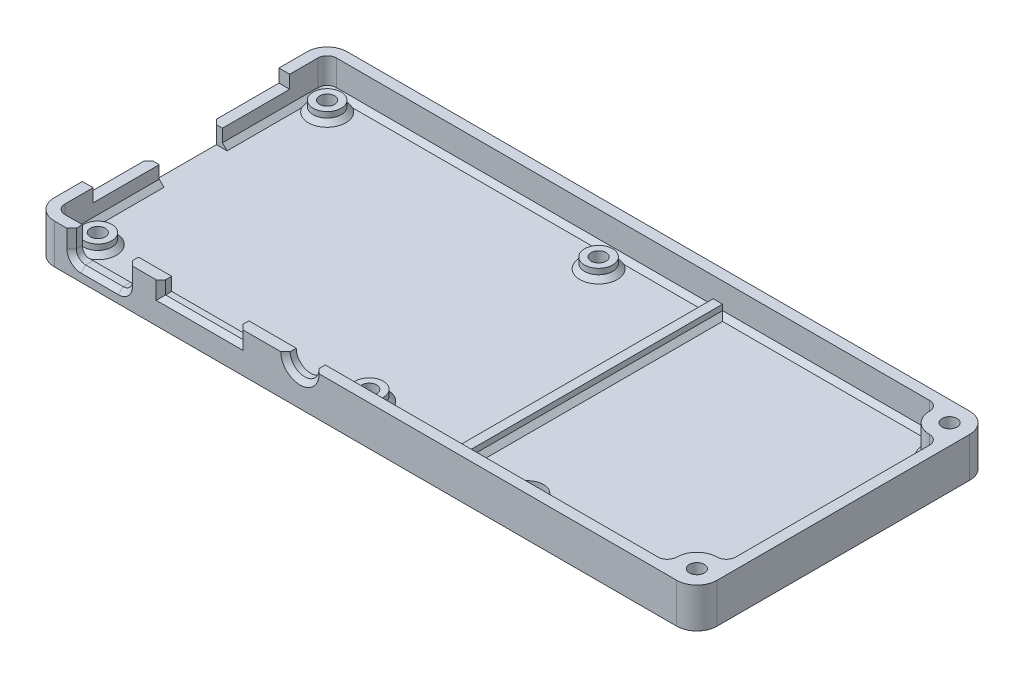
SolidWorks part; units mm, degrees
ref_plane "Front Plane" through (0, 0, 0) normal (0, 0, 1) x (1, 0, 0)
ref_plane "Top Plane" through (0, 0, 0) normal (0, 1, 0) x (1, 0, 0)
ref_plane "Right Plane" through (0, 0, 0) normal (1, 0, 0) x (0, 0, -1)
sketch "Sketch1" plane through (0, 0, 0) normal (0, 1, 0) x (1, 0, 0)
  line L0 (-71.5618, 3.106) -> (63.4382, 3.106) construction
  line L1 (-71.5618, 31.106) -> (63.4382, 31.106)
  line L2 (-71.5618, 31.106) -> (-71.5618, -24.894)
  line L3 (-71.5618, -24.894) -> (63.4382, -24.894)
  line L4 (63.4382, 31.106) -> (63.4382, -24.894)
  line L5 (-60.6618, -24.894) -> (-60.6618, -31.6828) construction
  line L6 (-68.0618, 27.606) -> (-10.0618, 27.606)
  line L7 (-68.0618, 27.606) -> (-68.0618, -21.394)
  line L8 (-68.0618, -21.394) -> (-10.0618, -21.394)
  line L9 (-10.0618, 27.606) -> (-10.0618, -21.394)
  line L10 (-39.5618, -24.894) -> (-39.5618, -31.6828) construction
  line L11 (-18.0618, -24.894) -> (-18.0618, -31.6828) construction
  line L12 (-65.4118, -26.5648) -> (-55.9118, -26.5648) construction
  line L13 (-48.0618, -26.5648) -> (-31.0618, -26.5648) construction
  line L14 (-22.0618, -26.5648) -> (-14.0618, -26.5648) construction
  line L15 (-72.5618, 9.606) -> (-72.5618, -3.394) construction
  line L16 (-71.5618, 3.106) -> (-72.5618, 3.106) construction
  dimension "D1" = 135
  dimension "D2" = 56
  dimension "D3" = 49
  dimension "D4" = 58
  dimension "D5" = 3.5
  dimension "D6" = 3.5
  dimension "D7" = 10.9
  dimension "D8" = 32
  dimension "D9" = 53.5
  dimension "D10" = 2
  dimension "D11" = 13
  dimension "D12" = 9.5
  dimension "D13" = 17
  dimension "D14" = 8
sketch "Sketch3" plane through (0, 0, 0) normal (0, 1, 0) x (1, 0, 0)
  line L4 (66.7382, 34.406) -> (-74.8618, 34.406)
  line L5 (-74.8618, 34.406) -> (-74.8618, -28.194)
  line L6 (-74.8618, -28.194) -> (66.7382, -28.194)
  line L7 (66.7382, -28.194) -> (66.7382, 34.406)
  line L8 (64.4382, 32.106) -> (-72.5618, 32.106)
  line L9 (64.4382, -25.894) -> (64.4382, 32.106)
  line L10 (-72.5618, -25.894) -> (64.4382, -25.894)
  line L11 (-72.5618, 32.106) -> (-72.5618, -25.894)
  line L12 (64.4382, 32.106) -> (-72.5618, 32.106)
  line L13 (64.4382, -25.894) -> (64.4382, 32.106)
  line L14 (-72.5618, -25.894) -> (64.4382, -25.894)
  line L15 (-72.5618, 32.106) -> (-72.5618, -25.894)
  line L16 (-4.0618, 3.106) -> (-4.0618, 34.406) construction
  line L17 (-71.5618, 3.106) -> (63.4382, 3.106) construction
  line L20 (-74.8618, 3.106) -> (52.7382, 3.106) construction
  line L25 (66.7382, -28.194) -> (66.7382, 34.406) construction
  line L26 (64.4382, -25.894) -> (64.4382, 32.106) construction
  dimension "D1" = 1
  dimension "D2" = 2.3
extrude "Boss-Extrude1" add sketch "Sketch3" along normal blind 8.5
sketch "Sketch5" plane through (0, 0, 0) normal (0, 1, 0) x (1, 0, 0)
  line L1 (-72.5618, 32.106) -> (64.4382, 32.106)
  line L2 (-72.5618, 32.106) -> (-72.5618, -25.894)
  line L3 (-72.5618, -25.894) -> (64.4382, -25.894)
  line L4 (64.4382, 32.106) -> (64.4382, -25.894)
extrude "Boss-Extrude2" add sketch "Sketch5" along normal blind 2
sketch "Sketch6" plane through (0, 2, 0) normal (0, 1, 0) x (1, 0, 0)
  circle A0 centre (-68.0618, 27.606) radius 3
  circle A1 centre (-68.0618, -21.394) radius 3
  circle A2 centre (-10.0618, -21.394) radius 3
  circle A3 centre (-10.0618, 27.606) radius 3
extrude "Boss-Extrude3" add sketch "Sketch6" along normal blind 2.2
sketch "Sketch10" plane through (0, 2, 0) normal (0, 1, 0) x (1, 0, 0)
  line L0 (64.4382, 32.106) -> (-72.5618, 32.106) construction
  line L1 (9.9382, 32.106) -> (11.9382, 32.106)
  line L2 (9.9382, 32.106) -> (9.9382, -25.894)
  line L3 (9.9382, -25.894) -> (11.9382, -25.894)
  line L4 (11.9382, 32.106) -> (11.9382, -25.894)
  line L5 (-72.5618, -25.894) -> (64.4382, -25.894) construction
  line L6 (-10.0618, 27.606) -> (-10.0618, -21.394) construction
  dimension "D1" = 2
  dimension "D2" = 20
extrude "Boss-Extrude4" add sketch "Sketch10" along normal blind 2.2
sketch "Sketch11" plane through (0, 0, 28.194) normal (0, 0, 1) x (1, 0, 0)
  line L0 (-74.8618, 8.5) -> (-74.8618, 0) construction
  line L1 (-66.8618, 8.5) -> (-54.8618, 8.5)
  line L2 (-66.8618, 8.5) -> (-66.8618, 2.7)
  line L3 (-66.8618, 2.7) -> (-54.8618, 2.7)
  line L4 (-54.8618, 8.5) -> (-54.8618, 2.7)
  line L5 (-74.8618, 0) -> (66.7382, 0) construction
  line L6 (-60.8618, 8.5) -> (-60.6618, 0) construction
  line L7 (-65.4118, 0) -> (-55.9118, 0) construction
  line L9 (-47.778, 8.5) -> (-31.278, 8.5)
  line L10 (-47.778, 8.5) -> (-47.778, 5.7)
  line L11 (-47.778, 5.7) -> (-31.278, 5.7)
  line L12 (-31.278, 8.5) -> (-31.278, 5.7)
  line L13 (-68.0618, 0) -> (-10.0618, 0) construction
  line L14 (-39.5618, 0) -> (-39.528, 8.5) construction
  line L15 (-48.0618, 0) -> (-31.0618, 0) construction
  line L16 (-18.0618, 0) -> (-18.0618, 8.5) construction
  line L17 (-22.0618, 0) -> (-14.0618, 0) construction
  line L18 (-74.8618, 8.5) -> (66.7382, 8.5) construction
  circle A0 centre (-18.0618, 8.5) radius 3.1
  dimension "D5" = 6.2
  dimension "D1" = 2.7
  dimension "D2" = 12
  dimension "D3" = 5.7
  dimension "D4" = 16.5
  dimension "D6" = 8
  dimension "D7" = 5.8
  dimension "D8" = 2.8
extrude "Cut-Extrude1" cut sketch "Sketch11" against normal up to next
sketch "Sketch12" plane through (-74.8618, 0, 0) normal (-1, 0, 0) x (0, 0, 1)
  line L0 (-3.106, 0) -> (-3.106, 8.5) construction
  line L1 (-27.606, 0) -> (21.394, 0) construction
  line L2 (-34.406, 8.5) -> (28.194, 8.5) construction
  line L3 (-24.106, 5.7) -> (17.894, 5.7)
  line L4 (-9.7329, 5.7) -> (3.7671, 5.7)
  line L5 (-9.7329, 5.7) -> (-9.7329, 2)
  line L6 (-9.7329, 2) -> (3.7671, 2)
  line L7 (3.7671, 5.7) -> (3.7671, 2)
  line L8 (-24.106, 8.5) -> (17.894, 8.5)
  line L9 (-24.106, 8.5) -> (-24.106, 5.7)
  line L10 (-34.406, 0) -> (28.194, 0) construction
  line L11 (17.894, 8.5) -> (17.894, 5.7)
  line L12 (-9.7329, 3.85) -> (3.7671, 3.85) construction
  point P17 (-3.106, 5.7)
  dimension "D1" = 13.5
  dimension "D2" = 5.7
  dimension "D3" = 3.7
  dimension "D4" = 2
extrude "Cut-Extrude2" cut sketch "Sketch12" against normal up to next contours L9 L3 L11 L8 | L7 L6 L5 L4
fillet "Fillet6" radius 2 1 edges at (64.4382, 5.25, -32.106)
fillet "Fillet8" radius 2 2 edges at (-72.5618, 5.25, 25.894) (-72.5618, 5.25, -32.106)
chamfer "Chamfer1" distance 1 angle 45 4 edges at (-68.0618, 2, 24.394) (-10.0618, 2, 24.394) (-10.0618, 2, -24.606) (-68.0618, 2, -24.606)
sketch "Sketch24" plane through (0, 2, 0) normal (0, 1, 0) x (1, 0, 0)
  line L0 (11.9382, 3.106) -> (61.5789, 3.106) construction
  line L1 (11.9382, -25.894) -> (11.9382, 32.106) construction
  line L2 (66.7382, -28.194) -> (66.7382, 34.406) construction
  circle A0 centre (62.4382, -23.894) radius 4.3
  circle A1 centre (62.4382, 30.106) radius 4.3
  dimension "D1" = 4.3
extrude "Boss-Extrude7" add sketch "Sketch24" along normal up to surface (6.5 mm away) up to face at (-5.8784, 8.5, -11.175)
fillet "Fillet21" radius 2 1 edges at (58.6317, 5.25, 25.894)
fillet "Fillet22" radius 2 3 edges at (64.4382, 5.25, 20.0874) (64.4382, 5.25, -26.2994) (58.6317, 5.25, -32.106)
fillet "Fillet20" radius 4.3 4 edges at (66.7382, 4.25, 28.194) (-74.8618, 4.25, -34.406) (-74.8618, 4.25, 28.194) (66.7382, 4.25, -34.406)
fillet "Fillet23" radius 2 2 edges at (-66.8618, 2.7, 27.044) (-54.8618, 2.7, 27.044)
chamfer "Chamfer5" distance 1 angle 45 17 edges at (-72.5618, 2, 13.8305) (-72.5618, 2, -19.9195) (-71.976, 2, 25.3082) (-71.976, 2, -31.5202) (-30.3118, 2, 25.894) (-30.3118, 2, -32.106) (9.9382, 2, -3.106) (11.9382, 2, -3.106) (34.0382, 2, -32.106) (34.0382, 2, 25.894) (59.3977, 2, 20.8534) (64.4382, 2, -3.106) (59.3977, 2, -27.0654) (57.5524, 2, 25.3082) (63.8524, 2, 19.0082) (63.8524, 2, -25.2202) (57.5524, 2, -31.5202)
hole_wizard "Ø3.2 (3.2) Diameter Hole1" positions "Sketch28" profile "Sketch27" hole size "Ø3.2" standard "ANSI Metric"
sketch "Sketch28" plane through (0, 0, 0) normal (0, -1, 0) x (-1, 0, 0)
  point P0 (68.0618, 27.606)
  point P4 (68.0618, -21.394)
  point P8 (-62.4382, 30.106)
  point P12 (-62.4382, -23.894)
  point P15 (10.0618, -21.394)
  point P19 (10.0618, 27.606)
sketch "Sketch27" plane through (-68.0618, 0, -27.606) normal (1, 0, 0) x (0, 0, -1)
  line L0 (0, 0) -> (0, 12)
  line L1 (0, 12) -> (1.6, 12)
  line L2 (1.6, 12) -> (1.6, 0)
  line L5 (1.6, 0) -> (0, 0)
  line L10 (0, 12) -> (-1.6, 12) construction
  line L11 (0, -6.35) -> (0, 107.95) construction
  dimension "Hole Dia." = 3.2
  dimension "Hole Depth" = 12
  dimension "Drill Angle" = 180
chamfer "Chamfer6" distance 1 angle 45 9 edges at (-18.0618, 5.4, 28.194) (-31.278, 7.1, 28.194) (-39.528, 5.7, 28.194) (-47.778, 7.1, 28.194) (-54.8618, 6.6, 28.194) (-60.8618, 2.7, 28.194) (-66.8618, 6.6, 28.194) (-55.4476, 3.2858, 28.194) (-66.276, 3.2858, 28.194)
chamfer "Chamfer8" distance 1 angle 45 3 edges at (-74.8618, 2, -2.9829)
sketch "Sketch29" plane through (0, 2, 0) normal (0, 1, 0) x (1, 0, 0)
  circle A0 centre (23.9495, -21.5485) radius 3.3455
extrude "Cut-Extrude3" cut sketch "Sketch29" against normal blind 10
